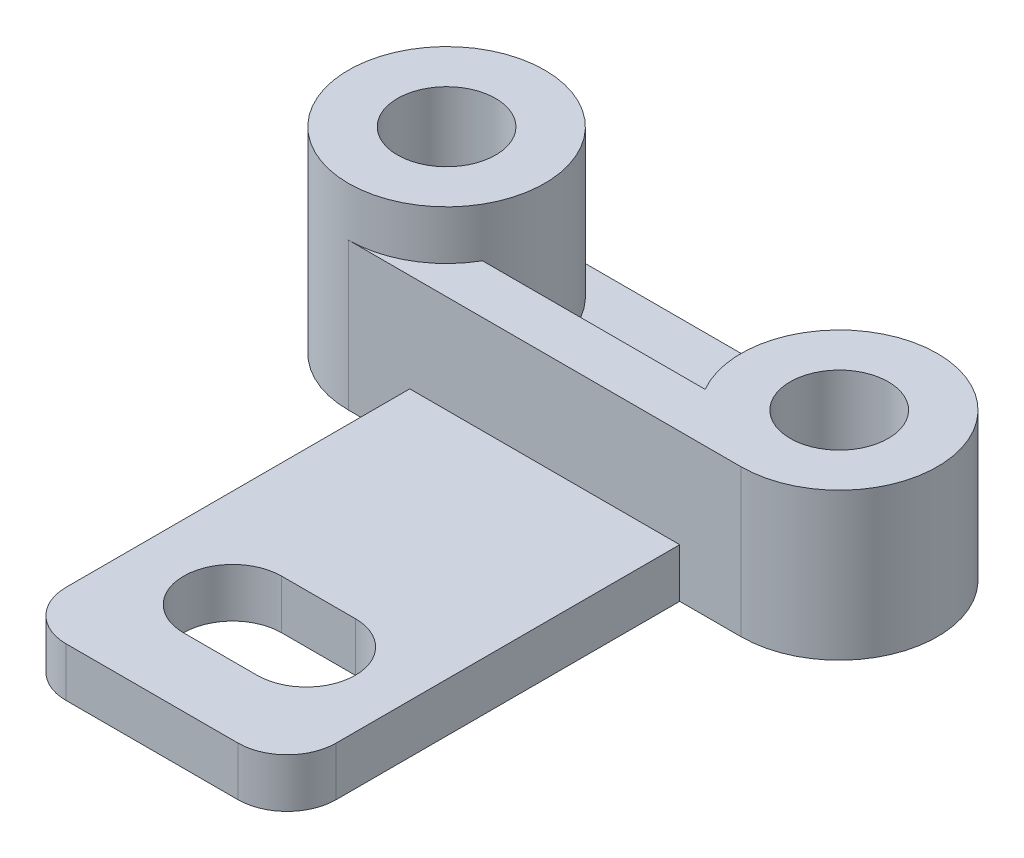
SolidWorks part; units mm, degrees
ref_plane "Front Plane" through (0, 0, 0) normal (0, 0, 1) x (1, 0, 0)
ref_plane "Top Plane" through (0, 0, 0) normal (0, 1, 0) x (1, 0, 0)
ref_plane "Right Plane" through (0, 0, 0) normal (1, 0, 0) x (0, 0, -1)
sketch "Sketch1" plane through (0, 0, 0) normal (0, 1, 0) x (1, 0, 0)
  line L0 (0, 0) -> (0, -52.1884) construction
  line L1 (-40, -50) -> (40, -50)
  line L2 (-40, -50) -> (-40, 50)
  line L3 (-40, 50) -> (40, 50)
  line L4 (40, -50) -> (40, 50)
  line L5 (-40, -50) -> (40, 50) construction
  line L6 (-40, 50) -> (40, -50) construction
  line L7 (-7.5, -26.0942) -> (7.5, -26.0942) construction
  line L8 (-7.5, -16.0942) -> (7.5, -16.0942)
  line L9 (-7.5, -36.0942) -> (7.5, -36.0942)
  line L10 (40, 30) -> (24, 30) construction
  line L11 (-27.5, -50) -> (27.5, -50)
  line L12 (-27.5, -50) -> (-27.5, 30)
  line L13 (-27.5, 30) -> (27.5, 30)
  line L14 (27.5, -50) -> (27.5, 30)
  line L15 (-27.5, 30) -> (-40, 30)
  line L16 (-40, 30) -> (40, 30)
  line L17 (-40, 70) -> (40, 70)
  circle A1 centre (-40, 50) radius 20
  circle A2 centre (-40, 50) radius 10
  circle A3 centre (40, 50) radius 20
  circle A4 centre (40, 50) radius 10
  arc A5 (-7.5, -16.0942) -> (-7.5, -36.0942) centre (-7.5, -26.0942) ccw
  arc A6 (7.5, -36.0942) -> (7.5, -16.0942) centre (7.5, -26.0942) ccw
  point P0 (0, 0)
  point P14 (0, -26.0942)
  dimension "D3" = 15
  dimension "D4" = 40
  dimension "D5" = 20
  dimension "D6" = 10
  dimension "D1" = 80
  dimension "D2" = 100
  dimension "D7" = 20
extrude "Boss-Extrude1" add sketch "Sketch1" along normal blind 10 contours A2 L3 A1 L2 | A2 L2 A1 L3 | L16 A3 L3 A1 L15 L13 | L3 A4 L4 A3 | L4 A4 L3 A3 | L1 L14 L13 L12 A6 L9 A5 L8 | L3 A3 L17 A1 region at (0, 0, 7.3891) region at (-59.4343, 0, -50) region at (0, 0, -39.0225) region at (-30.097, 0, -40.097) region at (0, 0, -60.9775) region at (53.7421, 0, -63.7421) region at (30.097, 0, -40.097)
sketch "Sketch2" plane through (0, 10, 0) normal (0, 1, 0) x (1, 0, 0)
  line L0 (40, 40) -> (-40, 40)
  line L1 (-40, 60) -> (40, 60)
  line L2 (-27.5, 30) -> (27.5, 30)
  line L6 (27.5, 30) -> (40, 30)
  line L7 (40, 70) -> (-40, 70)
  line L8 (-40, 30) -> (-27.5, 30)
  line L9 (-27.5, 30) -> (-27.5, -50)
  line L10 (-27.5, -50) -> (27.5, -50)
  line L11 (27.5, -50) -> (27.5, 30)
  line L12 (27.5, 30) -> (40, 30)
  line L13 (40, 70) -> (-40, 70)
  line L14 (-40, 30) -> (-27.5, 30)
  line L15 (-27.5, 30) -> (-27.5, -50)
  line L16 (-27.5, -50) -> (27.5, -50)
  line L17 (27.5, -50) -> (27.5, 30)
  circle A0 centre (-40, 50) radius 10 construction
  circle A1 centre (40, 50) radius 10 construction
  arc A2 (40, 30) -> (40, 70) centre (40, 50) ccw
  arc A3 (-40, 70) -> (-40, 30) centre (-40, 50) ccw
  arc A4 (40, 30) -> (40, 70) centre (40, 50) ccw
  arc A5 (-40, 70) -> (-40, 30) centre (-40, 50) ccw
  circle A6 centre (40, 50) radius 10
  circle A7 centre (-40, 50) radius 10
  circle A8 centre (40, 50) radius 20
  circle A9 centre (-40, 50) radius 20
  circle M9 centre (40, 50) radius 10
  line M10 (27.5, 30) -> (40, 30)
  arc M11 (40, 30) -> (40, 70) centre (40, 50) ccw
  arc M13 (-40, 70) -> (-40, 30) centre (-40, 50) ccw
  line M14 (-40, 30) -> (-27.5, 30)
  circle M18 centre (-40, 50) radius 10
  dimension "D1" = 0
extrude "Boss-Extrude2" add sketch "Sketch2" along normal blind 20 contours A9 L2 A8 L0 M14 M10 | L1 A8 L0 M9 | A8 L1 L0 M11 M9 | L0 A9 L1 M18 | A9 L0 L1 M13 M18 region at (47.4579, 10, -42.5421) region at (26.7001, 10, -50) region at (0, 10, -34.6013) region at (-30.2735, 10, -33.1533) region at (-26.7001, 10, -50)
extrude "Boss-Extrude3" add sketch "Sketch2<3>" along normal blind 30 contours A9 L0 L1 M13 M18 | L0 A9 L1 M18 region at (-30.2735, 10, -33.1533) region at (-26.7001, 10, -50)
sketch "Sketch2<3>" plane through (0, 10, 0) normal (0, 1, 0) x (1, 0, 0) same geometry as "Sketch2"
fillet "Fillet1" radius 10 2 edges at (-27.5, 5, 50) (27.5, 5, 50)
